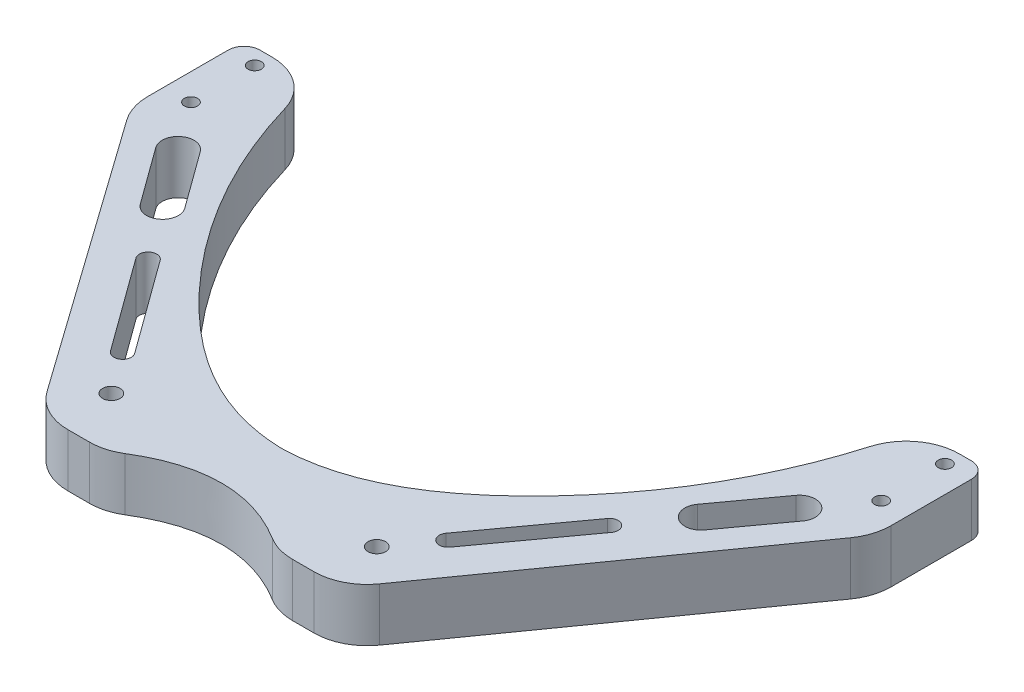
SolidWorks part; units mm, degrees
material "Hexcel AS4C (3000 丝)"
ref_plane "前视基准面" through (0, 0, 0) normal (0, 0, 1) x (1, 0, 0)
ref_plane "上视基准面" through (0, 0, 0) normal (0, 1, 0) x (1, 0, 0)
ref_plane "右视基准面" through (0, 0, 0) normal (1, 0, 0) x (0, 0, -1)
sketch "草图1" plane through (0, 0, 0) normal (0, 1, 0) x (1, 0, 0)
  line L0 (0, 0) -> (0, -31) construction
  line L1 (-65, 6) -> (65, 6) construction
  line L2 (-65, 6) -> (-65, -6) construction
  line L3 (-65, -6) -> (65, -6) construction
  line L4 (65, 6) -> (65, -6) construction
  line L5 (-65, 6) -> (65, -6) construction
  line L6 (-65, -6) -> (65, 6) construction
  line L8 (-70, -71) -> (70, -71)
  line L9 (-70, -71) -> (-70, 9)
  line L10 (-70, 9) -> (70, 9)
  line L11 (70, -71) -> (70, 9)
  line L12 (-70, -71) -> (70, 9) construction
  line L13 (-70, 9) -> (70, -71) construction
  circle A0 centre (-65, 6) radius 1.25
  circle A1 centre (-65, -6) radius 1.25
  circle A2 centre (65, -6) radius 1.25
  circle A3 centre (65, 6) radius 1.25
  circle A4 centre (-25, -61) radius 1.65
  circle A5 centre (25, -61) radius 1.65
  point P0 (0, 0)
  dimension "D3" = 2.5
  dimension "D7" = 3.3
  dimension "D8" = 50
  dimension "D9" = 10
  dimension "D1" = 130
  dimension "D2" = 12
  dimension "D4" = 5
  dimension "D5" = 3
  dimension "D6" = 80
extrude "凸台-拉伸1" add sketch "草图1" along normal blind 10
sketch "草图2" plane through (0, 10, 0) normal (0, 1, 0) x (1, 0, 0)
  line L0 (0, 9) -> (0, -71) construction
  line L1 (70, 9) -> (-70, 9) construction
  line L2 (-70, -71) -> (70, -71) construction
  line L3 (-70, -12.3319) -> (-28.346, -71)
  line L4 (-70, 9) -> (-70, -71) construction
  line L5 (70, -12.3319) -> (28.346, -71)
  line L6 (-16.1057, -71) -> (16.1057, -71)
  line L7 (28.346, -71) -> (70, -71)
  line L10 (70, -71) -> (70, 9)
  line L11 (70, 9) -> (-70, 9)
  line L12 (-70, 9) -> (-70, -71)
  line L13 (-70, -71) -> (70, -71)
  line L14 (70, -71) -> (70, -12.3319)
  line L15 (56.9068, 9) -> (-56.9068, 9)
  line L16 (-70, -12.3319) -> (-70, -71)
  line L17 (-70, -71) -> (-28.346, -71)
  spline S0 degree 3 poles (-56.9068, 9) (-53.2681, -8.5992) (-38.6301, -35.6405) (-12.8757, -53.6533) (0, -53.9363) knots 0 0 0 0 0.590583 1 1 1 1
  spline S1 degree 2 poles (-16.1057, -71) (0, -59.4621) (16.1057, -71) knots 0 0 0 1 1 1
  spline S2 degree 3 poles (56.9068, 9) (53.2681, -8.5992) (38.6301, -35.6405) (12.8757, -53.6533) (0, -53.9363) knots 0 0 0 0 0.590583 1 1 1 1
  dimension "D1" = 0
extrude "切除-拉伸1" cut sketch "草图2" against normal through all
fillet "圆角1" radius 10 9 edges at (-70, 5, 12.3319) (-56.9068, 5, -9) (70, 5, 12.3319) (56.9068, 5, -9) (0, 5, 53.9363) (-28.346, 5, 71) (-16.1057, 5, 71) (28.346, 5, 71) (16.1057, 5, 71)
fillet "圆角2" radius 3 2 edges at (-70, 5, -9) (70, 5, -9)
sketch "草图3" plane through (0, 10, 0) normal (0, 1, 0) x (1, 0, 0)
  line L0 (65, -6) -> (25, -61) construction
  line L1 (0, 0) -> (0, -99.6395) construction
  line L2 (30.6449, -53.2383) -> (43.4537, -35.6261) construction
  line L3 (29.3244, -52.2779) -> (42.1332, -34.6658)
  line L4 (31.9654, -54.1987) -> (44.7742, -36.5865)
  line L5 (58.5098, -14.924) -> (50.6958, -25.6682) construction
  line L6 (60.936, -16.6885) -> (53.122, -27.4327)
  line L7 (56.0836, -13.1595) -> (48.2696, -23.9037)
  line L8 (-58.5098, -14.924) -> (-50.6958, -25.6682) construction
  line L9 (-60.936, -16.6885) -> (-53.122, -27.4327)
  line L10 (-56.0836, -13.1595) -> (-48.2696, -23.9037)
  line L11 (-30.6449, -53.2383) -> (-43.4537, -35.6261) construction
  line L12 (-29.3244, -52.2779) -> (-42.1332, -34.6658)
  line L13 (-31.9654, -54.1987) -> (-44.7742, -36.5865)
  arc A0 (29.3244, -52.2779) -> (31.9654, -54.1987) centre (30.6449, -53.2383) ccw
  arc A1 (44.7742, -36.5865) -> (42.1332, -34.6658) centre (43.4537, -35.6261) ccw
  arc A2 (60.936, -16.6885) -> (56.0836, -13.1595) centre (58.5098, -14.924) ccw
  arc A3 (48.2696, -23.9037) -> (53.122, -27.4327) centre (50.6958, -25.6682) ccw
  arc A4 (-60.936, -16.6885) -> (-56.0836, -13.1595) centre (-58.5098, -14.924) cw
  arc A5 (-48.2696, -23.9037) -> (-53.122, -27.4327) centre (-50.6958, -25.6682) cw
  arc A6 (-29.3244, -52.2779) -> (-31.9654, -54.1987) centre (-30.6449, -53.2383) cw
  arc A7 (-44.7742, -36.5865) -> (-42.1332, -34.6658) centre (-43.4537, -35.6261) cw
  point P9 (37.0493, -44.4322)
  point P14 (54.6028, -20.2961)
  point P23 (-54.6028, -20.2961)
  point P30 (-37.0493, -44.4322)
  dimension "D1" = 3
extrude "切除-拉伸2" cut sketch "草图3" against normal through all
